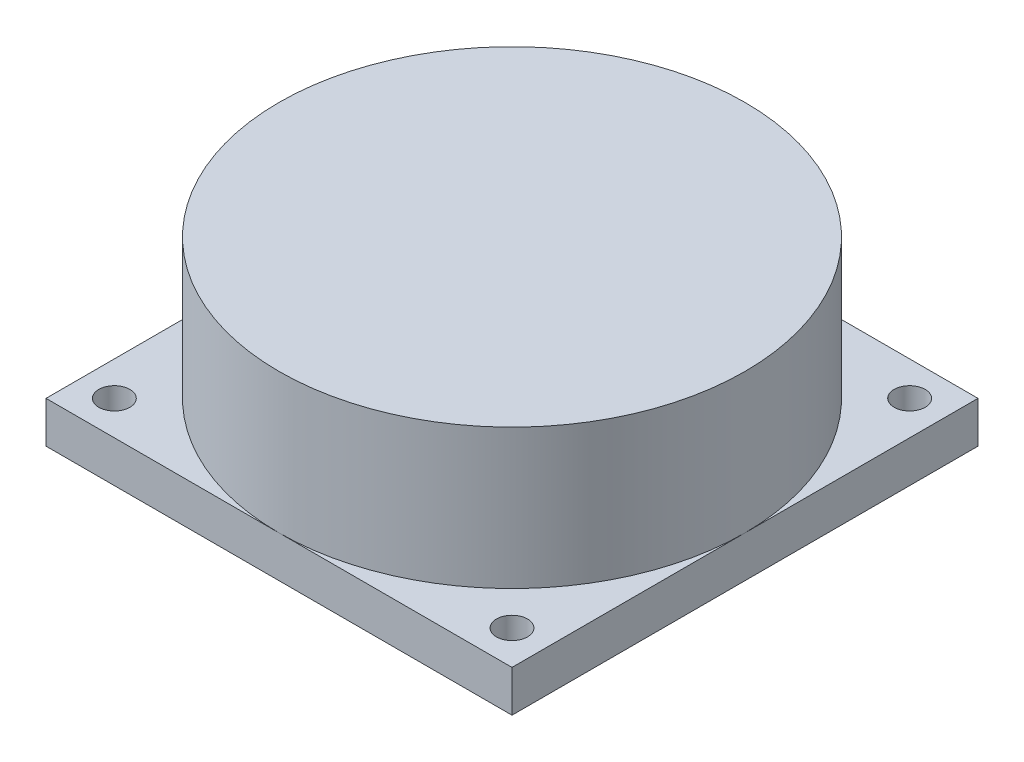
SolidWorks part; units mm, degrees
ref_plane "前视基准面" through (0, 0, 0) normal (0, 0, 1) x (1, 0, 0)
ref_plane "上视基准面" through (0, 0, 0) normal (0, 1, 0) x (1, 0, 0)
ref_plane "右视基准面" through (0, 0, 0) normal (1, 0, 0) x (0, 0, -1)
other "Configuration Table"
sketch "草图1" plane through (0, 0, 0) normal (0, 1, 0) x (1, 0, 0)
  line L1 (-22.5, 22.5) -> (22.5, 22.5)
  line L2 (-22.5, 22.5) -> (-22.5, -22.5)
  line L3 (-22.5, -22.5) -> (22.5, -22.5)
  line L4 (22.5, 22.5) -> (22.5, -22.5)
  line L5 (-22.5, 22.5) -> (22.5, -22.5) construction
  line L6 (-22.5, -22.5) -> (22.5, 22.5) construction
  circle A0 centre (19.2, 19.2) radius 1.5
  circle A1 centre (0, 0) radius 22.5
  circle A2 centre (19.2, -19.2) radius 1.5
  circle A3 centre (-19.2, -19.2) radius 1.5
  circle A4 centre (-19.2, 19.2) radius 1.5
  point P0 (0, 0)
  point P19 (0, 0)
  dimension "D2" = 3
  dimension "D1" = 45
  dimension "D4" = 38.4
  dimension "D3" = 4
extrude "凸台-拉伸1" add sketch "草图1" along normal blind 4 contours A1 L2 L3 A3 | A1 L1 L2 A4 | A1 L4 L1 A0 | A1 | A1 L3 L4 A2 region at (-17.3541, 0, -17.3541) region at (17.3541, 0, -17.3541) region at (0, 0, 0) region at (-17.3541, 0, 17.3541) region at (17.3541, 0, 17.3541)
extrude "凸台-拉伸2" add sketch "草图1<3>" along normal blind 17.5 contours A1 region at (0, 0, 0)
sketch "草图1<3>" plane through (0, 0, 0) normal (0, 1, 0) x (1, 0, 0) same geometry as "草图1"
